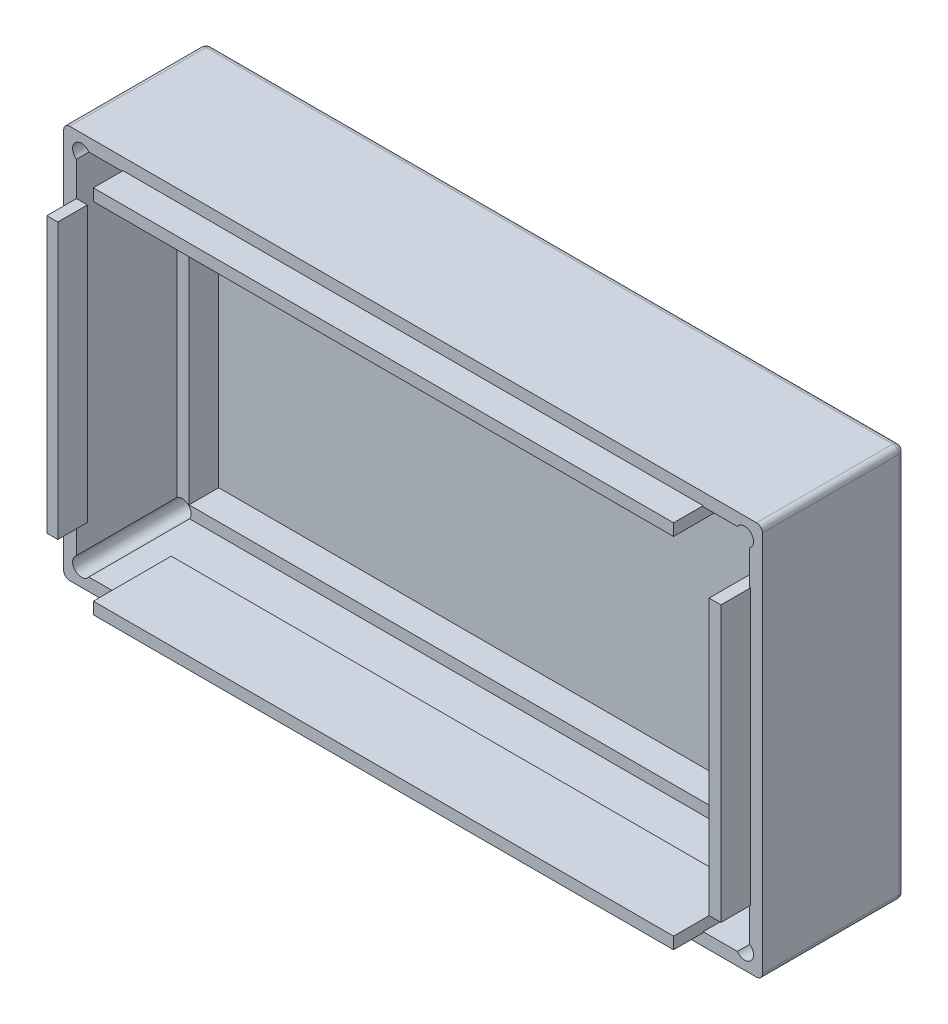
SolidWorks part; units mm, degrees
ref_plane "Front Plane" through (0, 0, 0) normal (0, 0, 1) x (1, 0, 0)
ref_plane "Top Plane" through (0, 0, 0) normal (0, 1, 0) x (1, 0, 0)
ref_plane "Right Plane" through (0, 0, 0) normal (1, 0, 0) x (0, 0, -1)
sketch "Sketch1" plane through (0, 0, 0) normal (0, 0, 1) x (1, 0, 0)
  line L1 (-55.6979, 33.2) -> (62.2021, 33.2)
  line L2 (-55.6979, 33.2) -> (-55.6979, -33.2)
  line L3 (-55.6979, -33.2) -> (62.2021, -33.2)
  line L4 (62.2021, 33.2) -> (62.2021, -33.2)
  line L5 (-55.6979, 33.2) -> (62.2021, -33.2) construction
  line L6 (-55.6979, -33.2) -> (62.2021, 33.2) construction
  point P0 (3.2521, 0)
  dimension "D1" = 66.4
  dimension "D2" = 117.9
extrude "Boss-Extrude1" add sketch "Sketch1" along normal blind 2
sketch "Sketch2" plane through (0, 0, 2) normal (0, 0, 1) x (1, 0, 0)
  line L0 (60.0521, -31.05) -> (60.0521, 31.05)
  line L1 (60.0521, 31.05) -> (-53.5479, 31.05)
  line L2 (-53.5479, 31.05) -> (-53.5479, -31.05)
  line L3 (-53.5479, -31.05) -> (60.0521, -31.05)
  line L12 (58.0521, -29.05) -> (58.0521, 29.05)
  line L13 (58.0521, 29.05) -> (-51.5479, 29.05)
  line L14 (-51.5479, 29.05) -> (-51.5479, -29.05)
  line L15 (-51.5479, -29.05) -> (58.0521, -29.05)
  line L16 (62.2021, 33.2) -> (-55.6979, 33.2) construction
  line L17 (-55.6979, 33.2) -> (-55.6979, -33.2) construction
  line L18 (-55.6979, -33.2) -> (62.2021, -33.2) construction
  line L19 (62.2021, -33.2) -> (62.2021, 33.2) construction
  dimension "D1" = 2.15
  dimension "D2" = 2.15
  dimension "D4" = 2.15
  dimension "D5" = 2.15
  dimension "D3" = 2
extrude "Boss-Extrude2" add sketch "Sketch2" along normal blind 5
sketch "Sketch3" plane through (0, 0, 0) normal (0, 0, -1) x (-1, 0, 0)
  line L0 (-62.2021, 33.2) -> (55.6979, 33.2) construction
  line L5 (-62.2021, -33.2) -> (-62.2021, 33.2) construction
  circle A0 centre (-59.2021, 30.2) radius 1.5
  dimension "D3" = 3
  dimension "D1" = 3
  dimension "D2" = 3
extrude "Cut-Extrude2" cut sketch "Sketch3" against normal through all both and the other way through all
mirror "Mirror2" about plane through (0, 0, 0) normal (0, 1, 0) of "Cut-Extrude2"
sketch "Sketch4" plane through (0, 0, 0) normal (0, 0, -1) x (-1, 0, 0)
  line L0 (-3.2521, 33.2) -> (-3.2521, -33.2) construction
  line L1 (-62.2021, 33.2) -> (55.6979, 33.2) construction
  line L2 (55.6979, -33.2) -> (-62.2021, -33.2) construction
  line L3 (-62.2021, 0) -> (55.6979, 0) construction
  line L4 (-62.2021, -33.2) -> (-62.2021, 33.2) construction
  line L5 (55.6979, 33.2) -> (55.6979, -33.2) construction
  dimension "D1" = 58.95
ref_plane "Plane1" through (3.2521, 0, 0) normal (1, 0, 0) x (0, 0, -1)
mirror "Mirror3" about plane through (0, 0, 0) normal (0, 1, 0) of "Cut-Extrude2" second plane through (3.2521, 0, 0) second plane normal (1, 0, 0)
fillet "Fillet1" radius 1 4 edges at (62.2021, -33.2, 1) (62.2021, 33.2, 1) (-55.6979, 33.2, 1) (-55.6979, -33.2, 1)
fillet "Fillet2" radius 1 12 edges at (62.2021, 0, 0) (3.2521, -33.2, 0) (-55.6979, 0, 0) (3.2521, 33.2, 0) (-55.405, -32.9071, 0) (-55.405, 32.9071, 0) (61.9092, 32.9071, 0) (61.9092, -32.9071, 0) (60.7021, 30.2, 0) (60.7021, -30.2, 0) (-51.1979, 30.2, 0) (-51.1979, -30.2, 0)
sketch "Sketch5" plane through (0, 0, 2) normal (0, 0, 1) x (1, 0, 0)
  line L0 (-51.462, -31.05) -> (57.9661, -31.05) construction
  line L1 (-53.5479, 28.9641) -> (-53.5479, -28.9641) construction
  line L2 (60.0521, -28.9641) -> (60.0521, 28.9641) construction
  line L3 (57.9661, 31.05) -> (-51.462, 31.05) construction
  line L4 (-54.6979, -33.2) -> (61.2021, -33.2)
  line L5 (62.2021, -32.2) -> (62.2021, 32.2)
  line L6 (61.2021, 33.2) -> (-54.6979, 33.2)
  line L7 (-55.6979, 32.2) -> (-55.6979, -32.2)
  line L8 (-54.6979, -33.2) -> (61.2021, -33.2)
  line L9 (62.2021, -32.2) -> (62.2021, 32.2)
  line L10 (61.2021, 33.2) -> (-54.6979, 33.2)
  line L11 (-55.6979, 32.2) -> (-55.6979, -32.2)
  line L12 (-51.462, -31.05) -> (57.9661, -31.05)
  line L13 (-53.5479, 28.9641) -> (-53.5479, -28.9641)
  line L14 (60.0521, -28.9641) -> (60.0521, 28.9641)
  line L15 (57.9661, 31.05) -> (-51.462, 31.05)
  arc A0 (57.9661, -31.05) -> (60.0521, -28.9641) centre (59.2021, -30.2) ccw construction
  arc A1 (-53.5479, -28.9641) -> (-51.462, -31.05) centre (-52.6979, -30.2) ccw construction
  arc A2 (-51.462, 31.05) -> (-53.5479, 28.9641) centre (-52.6979, 30.2) ccw construction
  arc A3 (60.0521, 28.9641) -> (57.9661, 31.05) centre (59.2021, 30.2) ccw construction
  arc A4 (61.2021, -33.2) -> (62.2021, -32.2) centre (61.2021, -32.2) ccw
  arc A5 (62.2021, 32.2) -> (61.2021, 33.2) centre (61.2021, 32.2) ccw
  arc A6 (-54.6979, 33.2) -> (-55.6979, 32.2) centre (-54.6979, 32.2) ccw
  arc A7 (-55.6979, -32.2) -> (-54.6979, -33.2) centre (-54.6979, -32.2) ccw
  arc A8 (61.2021, -33.2) -> (62.2021, -32.2) centre (61.2021, -32.2) ccw
  arc A9 (62.2021, 32.2) -> (61.2021, 33.2) centre (61.2021, 32.2) ccw
  arc A10 (-54.6979, 33.2) -> (-55.6979, 32.2) centre (-54.6979, 32.2) ccw
  arc A11 (-55.6979, -32.2) -> (-54.6979, -33.2) centre (-54.6979, -32.2) ccw
  arc A12 (57.9661, -31.05) -> (60.0521, -28.9641) centre (59.2021, -30.2) ccw
  arc A13 (-53.5479, -28.9641) -> (-51.462, -31.05) centre (-52.6979, -30.2) ccw
  arc A14 (-51.462, 31.05) -> (-53.5479, 28.9641) centre (-52.6979, 30.2) ccw
  arc A15 (60.0521, 28.9641) -> (57.9661, 31.05) centre (59.2021, 30.2) ccw
  dimension "D1" = 0
extrude "Boss-Extrude3" add sketch "Sketch5" along normal blind 22
sketch "Sketch7" plane through (0, 0, 24) normal (0, 0, 1) x (1, 0, 0)
  line L0 (3.2521, 33.2) -> (3.2521, -33.2) construction
  line L1 (-45.6979, 31.2) -> (52.2021, 31.2)
  line L2 (-53.6979, 23.2) -> (-53.6979, -23.2)
  line L3 (-45.6979, -31.2) -> (52.2021, -31.2)
  line L4 (60.2021, 23.2) -> (60.2021, -23.2)
  line L5 (-53.6979, 31.2) -> (-50.0473, 29.2) construction
  line L6 (-53.6979, -31.2) -> (-50.0473, -29.2) construction
  line L7 (61.2021, 33.2) -> (-54.6979, 33.2) construction
  line L8 (62.2021, -32.2) -> (62.2021, 32.2) construction
  line L9 (-51.6979, 23.2) -> (-51.6979, -23.2)
  line L10 (-51.6979, -29.2) -> (-50.0473, -29.2)
  line L11 (58.2021, 23.2) -> (58.2021, -23.2)
  line L12 (-51.6979, 29.2) -> (-50.0473, 29.2)
  line L13 (56.5514, 29.2) -> (60.2021, 31.2) construction
  line L14 (-45.6979, 31.2) -> (-45.6979, 29.2)
  line L15 (-45.6979, -45.3113) -> (52.2021, -45.3113)
  line L16 (52.2021, -31.2) -> (52.2021, -29.2)
  line L17 (-53.6979, 23.2) -> (-51.6979, 23.2)
  line L18 (-53.6979, -23.2) -> (-51.6979, -23.2)
  line L19 (-54.6979, -33.2) -> (61.2021, -33.2) construction
  line L20 (-55.6979, 32.2) -> (-55.6979, -32.2) construction
  line L21 (-53.6979, 31.2) -> (60.2021, 31.2) construction
  line L22 (-45.6979, 29.2) -> (52.2021, 29.2)
  line L23 (-51.6979, 29.2) -> (58.2021, 29.2) construction
  line L24 (-45.6979, 26.8172) -> (45.5995, -23.2) construction
  line L25 (-51.6979, 29.2) -> (-51.6979, -29.2) construction
  line L26 (-53.6979, 31.2) -> (-53.6979, -31.2) construction
  line L27 (-39.0954, -23.2) -> (3.2521, 0) construction
  line L28 (-45.6979, -29.2) -> (52.2021, -29.2)
  line L29 (-51.6979, -29.2) -> (58.2021, -29.2) construction
  line L30 (-53.6979, -31.2) -> (60.2021, -31.2) construction
  line L31 (-45.6979, -29.2) -> (-45.6979, -31.2)
  line L32 (58.2021, -23.2) -> (60.2021, -23.2)
  line L34 (52.2021, 29.2) -> (52.2021, 31.2)
  line L36 (56.5514, 29.2) -> (58.2021, 29.2)
  line L37 (58.2021, 29.2) -> (58.2021, -29.2) construction
  line L38 (58.2021, 23.2) -> (60.2021, 23.2)
  line L39 (60.2021, 31.2) -> (60.2021, -31.2) construction
  point P0 (3.2521, 0)
  line M25 (-53.5479, -28.9641) -> (-53.5479, 28.9641)
  dimension "D1" = 2
  dimension "D2" = 2
  dimension "D4" = 10
  dimension "D5" = 10
  dimension "D6" = 10
  dimension "D7" = 10
  dimension "D3" = 2
extrude "Boss-Extrude4" add sketch "Sketch7" along normal blind 5 contours L18 L9 L17 M25 | L22 L34 L1 L14 | L28 L16 L3 L31 | L11 L32 L4 L38
chamfer "Chamfer1" distance 10 angle 45 2 edges at (3.2521, -31.05, 24) (3.2521, 31.05, 24)
chamfer "Chamfer2" distance 10 angle 45 1 edges at (60.0521, 0, 24)
sketch "Sketch8" plane through (0, 0, 2) normal (0, 0, 1) x (1, 0, 0)
  line L0 (-55.6979, 15.2) -> (78.7066, 15.2) construction
  line L1 (-55.6979, 32.2) -> (-55.6979, -32.2) construction
  line L2 (-0.6979, 33.2) -> (-0.6979, -33.2) construction
  line L3 (61.2021, 33.2) -> (-54.6979, 33.2) construction
  line L4 (-54.6979, -33.2) -> (61.2021, -33.2) construction
  line L5 (-60.8907, 26.2) -> (77.9696, 26.2) construction
  line L6 (11.3021, 40.6838) -> (11.3021, -15.3608) construction
  line L7 (-0.6979, 26.2) -> (11.3021, 26.2)
  line L8 (11.3021, 26.2) -> (11.3021, 15.2)
  line L9 (11.3021, 15.2) -> (-0.6979, 15.2)
  line L10 (-0.6979, 15.2) -> (-0.6979, 26.2)
  dimension "D1" = 7
  dimension "D2" = 18
  dimension "D3" = 55
  dimension "D4" = 12
extrude "Cut-Extrude3" cut sketch "Sketch8" against normal blind 5
fillet "Fillet3" radius 1 7 edges at (-0.6979, 20.7, 2) (11.3021, 20.7, 2) (5.3021, 26.2, 0) (5.3021, 26.2, 2) (-0.6979, 20.7, 0) (11.3021, 20.7, 0) (5.3021, 15.2, 0)
